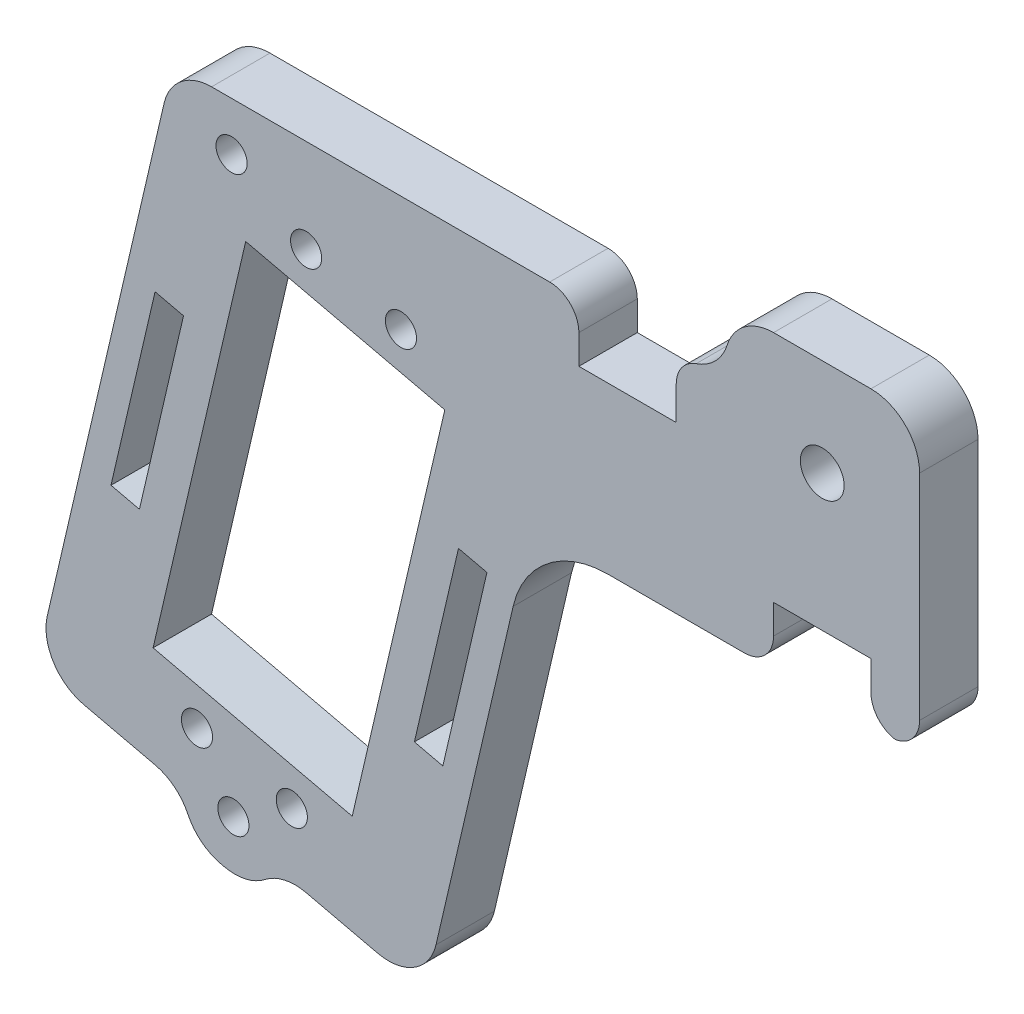
SolidWorks part; units mm, degrees
material "MDF"
ref_plane "Plano frontal" through (0, 0, 0) normal (0, 0, 1) x (1, 0, 0)
ref_plane "Plano superior" through (0, 0, 0) normal (0, 1, 0) x (1, 0, 0)
ref_plane "Plano direito" through (0, 0, 0) normal (1, 0, 0) x (0, 0, -1)
sketch "Esboço1" plane through (0, 0, 0) normal (0, 0, 1) x (1, 0, 0)
  line L0 (0, 20) -> (0, 0) construction
  line L5 (15, 16) -> (18, 16) construction
  line L6 (18, 6) -> (18, 16) construction
  line L15 (10, 11) -> (-10, 11) construction
  line L16 (15, 6) -> (18, 6) construction
  line L21 (-15, 6) -> (-18, 6) construction
  line L22 (-15, 6) -> (-15, 16) construction
  line L27 (-15, 16) -> (-18, 16) construction
  line L28 (-18, 6) -> (-18, 16) construction
  line L29 (-15, 6) -> (-18, 16) construction
  line L30 (-15, 16) -> (-18, 6) construction
  line L35 (15, 6) -> (15, 16) construction
  line L36 (23, 0) -> (23, 23)
  line L37 (23, 23) -> (-66.701, 23)
  line L43 (-29.9553, 0) -> (23, 0)
  line L61 (-68.7379, -29.9136) -> (-59.2257, 10.995)
  line L66 (-59.2257, 10.995) -> (-38.7714, 6.2389)
  line L67 (-38.7714, 6.2389) -> (-48.2836, -34.6697)
  line L68 (-48.2836, -34.6697) -> (-68.7379, -29.9136)
  line L69 (-63.9818, -9.4593) -> (-43.5275, -14.2154) construction
  line L74 (-48.9985, 8.617) -> (-58.5107, -32.2917) construction
  line L75 (-61.7051, 0.3321) -> (-41.2508, -4.424) construction
  line L80 (-38.7714, 6.2389) -> (-38.7714, -27.2218) construction
  line L85 (0, 20) -> (-15.8727, -48.263) construction
  line L86 (5, 0) -> (-5, 0)
  line L87 (-66.701, 23) -> (-80.7429, -37.389)
  line L88 (-80.7429, -37.389) -> (-40.8082, -46.6747)
  line L89 (-40.8082, -46.6747) -> (-29.9553, 0)
  line L93 (-65.6456, -40.8994) -> (-66.4949, -44.552)
  line L94 (-66.4949, -44.552) -> (-56.7548, -46.8168)
  line L95 (-55.9055, -43.1642) -> (-56.7548, -46.8168)
  line L96 (-47.0168, 17.1396) -> (-48.1492, 12.2695) construction
  line L97 (-48.1492, 12.2695) -> (-53.0193, 13.4019) construction
  line L98 (5, 0) -> (5, 6)
  line L99 (5, 6) -> (-5, 6)
  line L100 (-5, 0) -> (-5, 6)
  line L101 (0, 6) -> (0, 0) construction
  line L102 (5, 3) -> (-5, 3) construction
  line L103 (-10, 23) -> (-10, 30)
  line L104 (-10, 30) -> (10, 30)
  line L105 (10, 30) -> (10, 23)
  line L106 (10, 23) -> (10, 0)
  line L107 (-73.0647, -17.6141) -> (-70.1427, -18.2935)
  line L108 (-70.1427, -18.2935) -> (-65.6131, 1.1868)
  line L109 (-65.6131, 1.1868) -> (-68.5351, 1.8662)
  line L110 (-38.9742, -25.5409) -> (-41.8962, -24.8615)
  line L111 (-37.3666, -5.3812) -> (-34.4446, -6.0606)
  line L112 (-41.8962, -24.8615) -> (-37.3666, -5.3812)
  line L113 (-68.5351, 1.8662) -> (-73.0647, -17.6141)
  line L114 (-15, 17) -> (-25, 17)
  line L115 (-15, 17) -> (-15, 23)
  line L116 (-15, 23) -> (-25, 23)
  line L117 (-25, 17) -> (-25, 23)
  line L118 (-20, 23) -> (-20, 17) construction
  line L119 (-15, 20) -> (-25, 20) construction
  line L120 (-34.4446, -6.0606) -> (-38.9742, -25.5409)
  circle A0 centre (0, 20) radius 2.25
  circle A1 centre (10, 11) radius 1.6 construction
  circle A2 centre (-10, 11) radius 1.6 construction
  circle A8 centre (-64.2301, -34.8118) radius 1.6
  circle A9 centre (-54.49, -37.0766) radius 1.6
  circle A10 centre (-43.2792, 11.1371) radius 1.6
  circle A11 centre (-53.0193, 13.4019) radius 1.6
  circle A12 centre (-47.0168, 17.1396) radius 1.6 construction
  circle A15 centre (-60.4925, -40.8143) radius 1.6
  circle A16 centre (-60.6769, 18) radius 1.6
  point P0 (0, 20)
  point P13 (-16.5, 11)
  point P39 (-51.4779, -2.046)
  point P49 (0, 3)
  point P61 (0, 11)
  point P62 (-67.8779, -8.5534)
  point P66 (-30, 23)
  point P68 (0, 30)
  point P69 (-20, 20)
  point P78 (0, 0)
  point P79 (-5, 0)
  point P83 (0, 0)
  dimension "D1" = 4.5
  dimension "D3" = 3.2
  dimension "D11" = 14.6974
  dimension "D12" = 56
  dimension "D9" = 49.5
  dimension "D30" = 5
  dimension "D33" = 5
  dimension "D34" = 7
  dimension "D2" = 20
  dimension "D4" = 5
  dimension "D5" = 21
  dimension "D6" = 10
  dimension "D7" = 3
  dimension "D8" = 42
  dimension "D10" = 10
  dimension "D13" = 20
  dimension "D14" = 10
  dimension "D15" = 10
  dimension "D16" = 10
  dimension "D17" = 6
  dimension "D18" = 5
  dimension "D19" = 7
  dimension "D20" = 6
  dimension "D21" = 13.09
  dimension "D22" = 10
  dimension "D23" = 10
  dimension "D24" = 5
  dimension "D25" = 5
  dimension "D26" = 20
  dimension "D27" = 3
  dimension "D28" = 20
  dimension "D32" = 4
extrude "Ressalto-extrusão1" add sketch "Esboço1" along normal blind 6 contours L37 L87 L88 L89 L43 A12 A9 A8 A0 L67 L68 L61 L66 L21 L28 L27 L22 L86 L100 L99 L98 A10 A11 | L104 L103 L37 | L95 L88 L93 L94 A15 region at (-39.0316, -2.4357, 0) region at (0, 26.5, 0) region at (-61.2053, -43.8799, 0)
fillet "Filete1" radius 10 1 edges at (-29.9553, 0, 3)
fillet "Filete2" radius 5 7 edges at (-66.701, 23, 3) (-80.7429, -37.389, 3) (-66.4949, -44.552, 3) (-56.7548, -46.8168, 3) (-40.8082, -46.6747, 3) (-10, 30, 3) (10, 30, 3)
fillet "Filete4" radius 5 3 edges at (-65.6456, -40.8994, 3) (-55.9055, -43.1642, 3) (-10, 23, 3)
fillet "Filete5" radius 3 5 edges at (-25, 23, 3) (-15, 23, 3) (-5, 0, 3) (10, 0, 3) (5, 0, 3)
